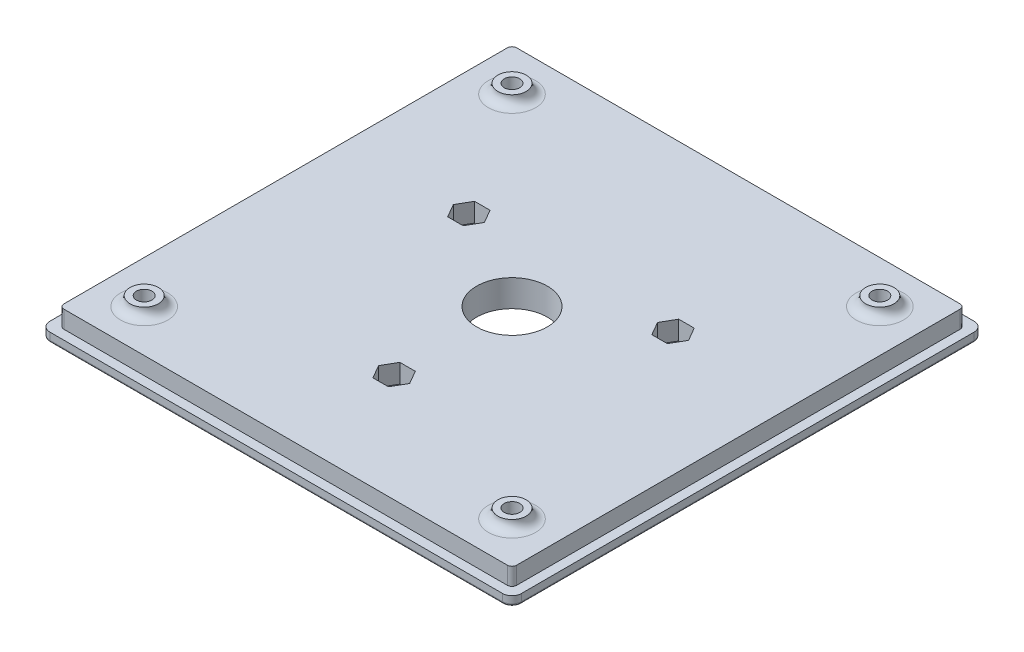
SolidWorks part; units mm, degrees
other "Câmera1"
ref_plane "Front" through (0, 0, 0) normal (0, 0, 1) x (1, 0, 0)
ref_plane "Top" through (0, 0, 0) normal (0, 1, 0) x (1, 0, 0)
ref_plane "Right" through (0, 0, 0) normal (1, 0, 0) x (0, 0, -1)
sketch "Sketch1" plane through (0, 0, 0) normal (0, 1, 0) x (1, 0, 0)
  line L1 (-50, 50) -> (50, 50)
  line L2 (-50, 50) -> (-50, -50)
  line L3 (-50, -50) -> (50, -50)
  line L4 (50, 50) -> (50, -50)
  line L5 (-50, 50) -> (50, -50) construction
  line L6 (-50, -50) -> (50, 50) construction
  dimension "D1" = 50
  dimension "D2" = 100
  dimension "D3" = 100
  dimension "D4" = 50
extrude "Boss-Extrude1" add sketch "Sketch1" along normal blind 2
sketch "Sketch4" plane through (0, 2, 0) normal (0, 1, 0) x (1, 0, 0)
  line L18 (-48, 48) -> (-48, -48)
  line L19 (-48, -48) -> (48, -48)
  line L20 (48, -48) -> (48, 48)
  line L21 (48, 48) -> (-48, 48)
  line L22 (-48, 48) -> (-48, -48)
  line L23 (-48, -48) -> (48, -48)
  line L24 (48, -48) -> (48, 48)
  line L25 (48, 48) -> (-48, 48)
  dimension "D1" = 2
extrude "Boss-Extrude3" add sketch "Sketch4" along normal blind 3.7
sketch "Sketch5" plane through (0, 5.7, 0) normal (0, 1, 0) x (1, 0, 0)
  circle A4 centre (-39, 39) radius 1.65
  circle A5 centre (39, -39) radius 1.65
  circle A6 centre (-39, -39) radius 1.65
  circle A7 centre (39, 39) radius 1.65
  point P0 (39, 39)
  point P2 (-39, 39)
  point P3 (-134.5938, 27.9973)
  point P6 (-39, -39)
  point P9 (39, -39)
  dimension "D1" = 3.3
  dimension "D2" = 3.3
  dimension "D3" = 3.3
  dimension "D4" = 3.3
  dimension "D5" = 39
  dimension "D7" = 39
  dimension "D8" = 39
  dimension "D9" = 39
  dimension "D10" = 39
  dimension "D11" = 39
  dimension "D12" = 39
  dimension "D6" = 39
extrude "Cut-Extrude1" cut sketch "Sketch5" against normal through all
sketch "Sketch6" plane through (0, 0, 0) normal (0, -1, 0) x (1, 0, 0)
  circle A6 centre (39, -39) radius 3
  circle A7 centre (-39, -39) radius 3
  circle A8 centre (-39, 39) radius 3
  circle A9 centre (39, 39) radius 3
  dimension "D1" = 6
  dimension "D2" = 6
  dimension "D3" = 6
  dimension "D4" = 6
extrude "Cut-Extrude2" cut sketch "Sketch6" against normal blind 3.5
fillet "Filete1" radius 0.5 4 edges at (50, 0, 0) (0, 0, -50) (0, 0, 50) (-50, 0, 0)
sketch "Sketch7" plane through (0, 3.5, 0) normal (0, -1, 0) x (-1, 0, 0)
  line L0 (-36.4945, 40.65) -> (-41.5055, 40.65)
  line L3 (-36.4945, 37.35) -> (-41.5055, 37.35)
  circle A0 centre (-39, 39) radius 3 construction
  circle A2 centre (-39, 39) radius 3
  circle A3 centre (-39, 39) radius 1.65 construction
  circle M28 centre (-39, 39) radius 3
  circle M29 centre (-39, 39) radius 1.65
extrude "Cut-Extrude3" cut sketch "Sketch7" against normal blind 0.6 contours L3 L0 M29 M28 | L3 L0 M28 M29 | A2
fillet "Fillet1" radius 2 8 edges at (-49.8536, 0.1464, -49.8536) (-49.8536, 0.1464, 49.8536) (49.8536, 0.1464, 49.8536) (49.8536, 0.1464, -49.8536) (50, 1.25, -50) (50, 1.25, 50) (-50, 1.25, 50) (-50, 1.25, -50)
fillet "Fillet2" radius 1 4 edges at (48, 3.85, -48) (48, 3.85, 48) (-48, 3.85, -48) (-48, 3.85, 48)
sketch "Sketch14" plane through (0, 4.1, 0) normal (0, -1, 0) x (1, 0, 0)
  line L0 (39, -40.65) -> (36.4945, -40.65)
  line L1 (39, -40.65) -> (41.5055, -40.65)
  line L2 (39, -37.35) -> (41.5055, -37.35)
  line L3 (39, -37.35) -> (36.4945, -37.35)
  line L4 (40.65, -39) -> (40.65, -40.65)
  line L5 (40.65, -39) -> (40.65, -37.35)
  line L6 (37.35, -39) -> (37.35, -40.65)
  line L7 (37.35, -39) -> (37.35, -37.35)
  arc A0 (41.5055, -40.65) -> (41.5055, -37.35) centre (39, -39) ccw
  circle A1 centre (39, -39) radius 1.65
  arc A2 (36.4945, -37.35) -> (36.4945, -40.65) centre (39, -39) ccw
  arc M3 (41.5055, -40.65) -> (41.5055, -37.35) centre (39, -39) ccw
  line M11 (41.5055, -37.35) -> (39, -37.35)
  dimension "D1" = 6
  dimension "D2" = 3.3
extrude "Boss-Extrude7" add sketch "Sketch14" along normal blind 0.3 contours L5 L4 L1 M3 M11 | L3 A2 L0 L6 L7
pattern_linear "LPattern1" count 2 spacing 78 along (-1, 0, 0) count 2 spacing 78 along (0, 0, 1) of "Cut-Extrude3"
pattern_linear "LPattern2" count 2 spacing 78 along (-1, 0, 0) count 2 spacing 78 along (0, 0, 1) of "Boss-Extrude7"
sketch "Sketch15" plane through (0, 5.7, 0) normal (0, 1, 0) x (1, 0, 0)
  circle A0 centre (39, 39) radius 3
  circle A1 centre (39, 39) radius 1.65
  dimension "D1" = 6
extrude "Boss-Extrude8" add sketch "Sketch15" along normal blind 2
pattern_linear "LPattern3" count 2 spacing 78 along (0, 0, 1) count 2 spacing 78 along (-1, 0, 0) of "Boss-Extrude8"
fillet "Fillet3" radius 2 4 edges at (39, 5.7, -36) (-39, 5.7, -36) (-39, 5.7, 42) (39, 5.7, 42)
sketch "Esboço1" plane through (0, 0, 0) normal (0, -1, 0) x (1, 0, 0)
  circle A0 centre (0, -25) radius 1.65
  dimension "D1" = 3.3
  dimension "D2" = 25
extrude "Corte-extrusão1" cut sketch "Esboço1" against normal through all
mirror "Espelhar1" about plane through (0, 0, 0) normal (0, 0, 1) of "Corte-extrusão1"
ref_plane "Plano2" through (0, 0, 0) normal (0.7071, 0, 0.7071) x (0.7071, 0, -0.7071)
sketch "Esboço2" plane through (0, 5.7, 0) normal (0, 1, 0) x (1, 0, 0)
  line L1 (1.6454, -27.85) -> (3.2909, -25)
  line L2 (3.2909, -25) -> (1.6454, -22.15)
  line L3 (1.6454, -22.15) -> (-1.6454, -22.15)
  line L4 (-1.6454, -22.15) -> (-3.2909, -25)
  line L5 (-3.2909, -25) -> (-1.6454, -27.85)
  line L6 (-1.6454, -27.85) -> (1.6454, -27.85)
  circle A0 centre (0, -25) radius 2.85 construction
  dimension "D1" = 5.7
extrude "Corte-extrusão3" cut sketch "Esboço2" against normal blind 4
sketch "Esboço3" plane through (0, 1.7, 0) normal (0, 1, 0) x (1, 0, 0)
  line L0 (2.3383, -26.65) -> (-2.3383, -26.65)
  line L1 (1.65, -23.35) -> (-1.65, -23.35)
  line L2 (1.65, -23.35) -> (1.65, -26.65)
  line L3 (1.65, -26.65) -> (-1.65, -26.65)
  line L4 (-1.65, -23.35) -> (-1.65, -26.65)
  line L5 (1.65, -23.35) -> (-1.65, -26.65) construction
  line L6 (1.65, -26.65) -> (-1.65, -23.35) construction
  line L7 (1.6454, -27.85) -> (3.2909, -25) construction
  line L8 (-3.2909, -25) -> (-1.6454, -27.85) construction
  line L9 (2.3383, -23.35) -> (-2.3383, -23.35)
  line L10 (3.2909, -25) -> (1.6454, -22.15) construction
  line L11 (-1.6454, -22.15) -> (-3.2909, -25) construction
  line L12 (2.3383, -26.65) -> (1.6454, -27.85)
  line L13 (1.6454, -27.85) -> (-1.6454, -27.85)
  line L14 (-1.6454, -27.85) -> (1.6454, -27.85) construction
  line L15 (-1.6454, -27.85) -> (1.6454, -27.85) construction
  line L16 (-1.6454, -27.85) -> (-2.3383, -26.65)
  line L17 (2.3383, -23.35) -> (1.6454, -22.15)
  line L18 (1.6454, -22.15) -> (-1.6454, -22.15)
  line L19 (-1.6454, -22.15) -> (-2.3383, -23.35)
  line L20 (2.3383, -26.65) -> (3.2909, -25)
  line L21 (3.2909, -25) -> (2.3383, -23.35)
  line L22 (2.3383, -26.65) -> (1.65, -26.65)
  line L23 (1.65, -25.2915) -> (1.65, -26.65)
  line L24 (2.3383, -23.35) -> (1.65, -23.35)
  line L25 (1.65, -23.35) -> (2.3383, -23.35)
  line L26 (2.3383, -23.35) -> (3.2909, -25)
  line L27 (3.2909, -25) -> (2.3383, -26.65)
  line L28 (2.3383, -26.65) -> (1.65, -26.65)
  line L29 (1.65, -26.65) -> (1.65, -23.35)
  point P0 (0, -25)
  dimension "D1" = 3.3
sketch "Esboço6" plane through (0, 5.7, 0) normal (0, 1, 0) x (1, 0, 0)
  circle A0 centre (0, 0) radius 7.5
  dimension "D1" = 15
extrude "Corte-extrusão4" cut sketch "Esboço6" against normal through all
sketch "Esboço8" plane through (0, 5.7, 0) normal (0, 1, 0) x (1, 0, 0)
  circle A0 centre (0, 25) radius 1.65
extrude "Ressalto-extrusão3" add sketch "Esboço8" against normal up to surface (5.7 mm away) up to face at (0, 0, 7.5)
pattern_circular "PadrãoCircular2" count 3 over 360 about axis through (0, 0, 0) along (0, 1, 0) of "Espelhar1", "Corte-extrusão3", "Corte-extrusão1"
sketch "Esboço10" plane through (0, 5.7, 0) normal (0, 1, 0) x (1, 0, 0)
  circle A0 centre (-21.6506, -12.5) radius 1.65
  circle A1 centre (21.6506, -12.5) radius 1.65
extrude "Ressalto-extrusão4" add sketch "Esboço10" against normal up to surface (5.7 mm away) up to face at (-23.0796, 0, 13.325)
sketch "Esboço11" plane through (0, 0, 0) normal (0, -1, 0) x (1, 0, 0)
  circle A0 centre (21.6506, -12.5) radius 1.8
  circle A1 centre (-21.6506, -12.5) radius 1.8
  circle A2 centre (0, 25) radius 1.8
  dimension "D1" = 3.6
extrude "Corte-extrusão5" cut sketch "Esboço11" against normal through all
